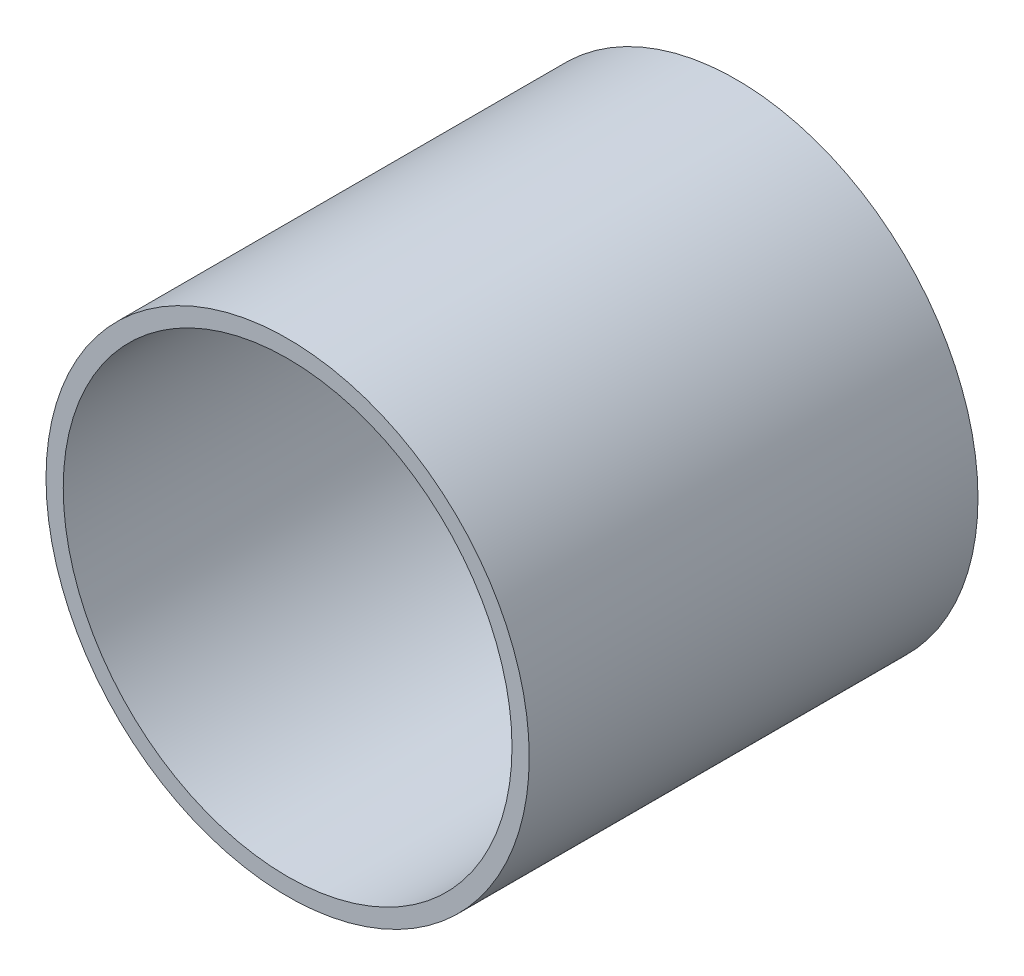
SolidWorks part; units mm, degrees
material "PLA"
ref_plane "Ebene vorne" through (0, 0, 0) normal (0, 0, 1) x (1, 0, 0)
ref_plane "Ebene oben" through (0, 0, 0) normal (0, 1, 0) x (1, 0, 0)
ref_plane "Ebene rechts" through (0, 0, 0) normal (1, 0, 0) x (0, 0, -1)
sketch "Skizze1" plane through (0, 0, 0) normal (0, 0, 1) x (1, 0, 0)
  circle A0 centre (0, 0) radius 26.375
  circle A1 centre (0, 0) radius 28.4
  dimension "D1" = 52.75
  dimension "D2" = 56.8
extrude "Aufsatz-Linear austragen1" add sketch "Skizze1" along normal blind 52.75
thread "Gewinde1" pitch 1 method cut trim with start face yes profile "Gewindeprofil1" start angle 0, offset 1, length 10, pitch 2, diameter 52.75
ref_plane "Ebene1" through (26.375, 0, -1) normal (0, -1, 0) x (1, 0, 0)
sketch "Gewindeprofil1" plane through (26.375, 0, -1) normal (0, -1, 0) x (1, 0, 0)
  line L0 (0, 0) -> (0, 1) construction
  line L1 (0, 0) -> (0.6766, 0.3906)
  line L2 (0.6766, 0.3906) -> (0.6766, 0.5469)
  line L3 (0.6766, 0.5469) -> (0, 0.9375)
  line L4 (0.6766, 0.4687) -> (0, 0.4687) construction
  line L11 (0, 0) -> (0, 0.9375)
  point P2 (0, 0)
  dimension "Pitch" = 1
  dimension "Profile_Angle" = 60
  dimension "Profile_Land" = 0.1562
  dimension "Profile_Height" = 0.6766
ref_plane "Ebene2" through (0, 0, 9.3) normal (0, 0, -1) x (-1, 0, 0)
sketch "Skizze4" plane through (0, 0, 9.3) normal (0, 0, -1) x (-1, 0, 0)
  circle A0 centre (0, 0) radius 25.475
  circle A1 centre (0, 0) radius 27.3217
  arc A2 (-25.8596, 5.1886) -> (26.375, 0) centre (0, 0) ccw construction
  dimension "D1" = 0.9
extrude "Aufsatz-Linear austragen2" add sketch "Skizze4" against normal blind 1
chamfer "Fase1" distance 1 angle 45 1 edges at (-26.375, 0, 10.3)
